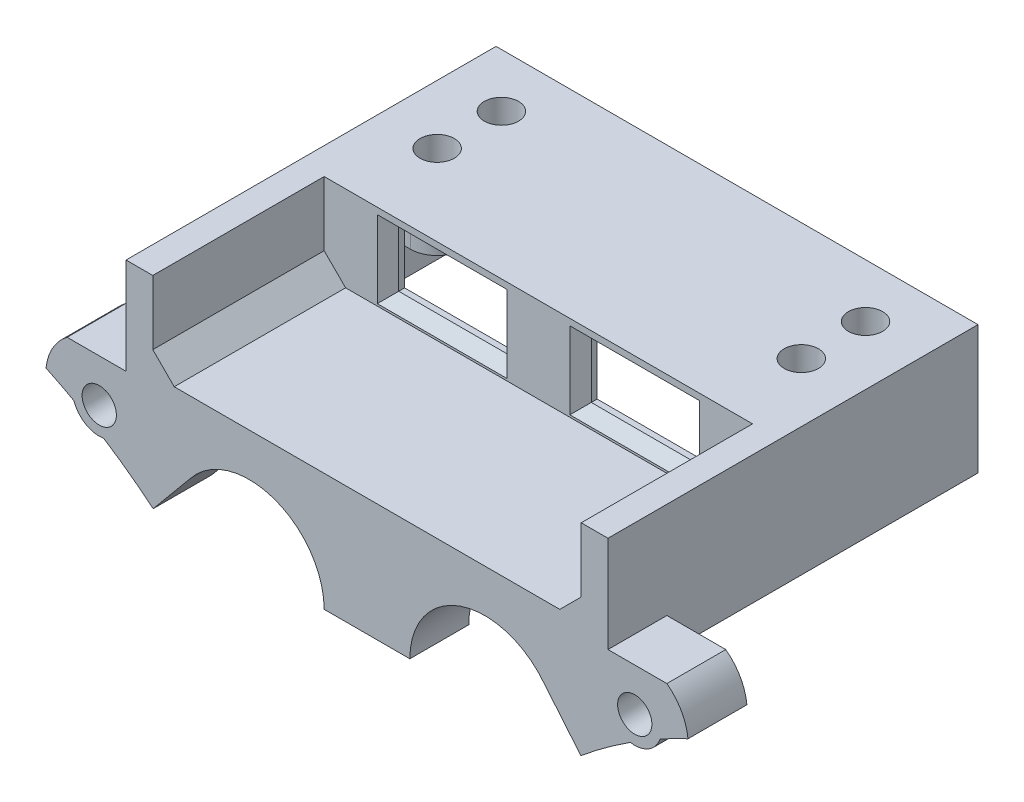
SolidWorks part; units mm, degrees
ref_plane "前视基准面" through (0, 0, 0) normal (0, 0, 1) x (1, 0, 0)
ref_plane "上视基准面" through (0, 0, 0) normal (0, 1, 0) x (1, 0, 0)
ref_plane "右视基准面" through (0, 0, 0) normal (1, 0, 0) x (0, 0, -1)
sketch "草图1" plane through (0, 0, 0) normal (0, 0, 1) x (1, 0, 0)
  line L0 (0, 0) -> (22.5, 0)
  line L1 (22.5, 0) -> (22.5, 12)
  line L2 (22.5, 12) -> (-22.5, 12)
  line L3 (-22.5, 12) -> (-22.5, 0)
  line L4 (-22.5, 0) -> (0, 0)
extrude "凸台-拉伸1" add sketch "草图1" along normal blind 34.55
sketch "草图2" plane through (0, 0, 34.55) normal (0, 0, 1) x (1, 0, 0)
  line L0 (-20, 12) -> (20, 12)
  line L1 (22.5, 12) -> (-22.5, 12) construction
  line L2 (20, 12) -> (20, 4)
  line L3 (20, 4) -> (-20, 4)
  line L4 (0, -6.6) -> (0, 6.6) construction
  line L5 (-20, 12) -> (-20, 4)
  point P9 (0, 4)
  point P10 (0, 12)
extrude "切除-拉伸1" cut sketch "草图2" against normal blind 16
sketch "草图3" plane through (0, 0, 0) normal (0, -1, 0) x (1, 0, 0)
  line L1 (0, 2) -> (20, 2)
  line L2 (20, 2) -> (20, 17)
  line L3 (20, 17) -> (-20, 17)
  line L4 (-20, 17) -> (-20, 2)
  line L5 (-20, 2) -> (0, 2)
extrude "切除-拉伸2" cut sketch "草图3" against normal blind 10
sketch "草图4" plane through (0, 0, 18.55) normal (0, 0, 1) x (1, 0, 0)
  line L0 (-14.04, 10.4) -> (-14.04, 5.2)
  line L1 (-13.94, 10.3) -> (-13.94, 5.3) construction
  line L7 (-13.94, 5.3) -> (-4.04, 5.3) construction
  line L8 (-13.94, 10.3) -> (-4.04, 10.3) construction
  line L9 (-4.04, 10.3) -> (-4.04, 5.3) construction
  line L10 (-14.04, 5.2) -> (-3.94, 5.2)
  line L11 (-3.94, 10.4) -> (-3.94, 5.2)
  line L12 (-14.04, 10.4) -> (-3.94, 10.4)
  line L13 (0, -6.6) -> (0, 6.6) construction
  line L14 (4.04, 10.3) -> (4.04, 5.3) construction
  line L15 (13.94, 10.3) -> (4.04, 10.3) construction
  line L16 (13.94, 5.3) -> (4.04, 5.3) construction
  line L17 (13.94, 10.3) -> (13.94, 5.3) construction
  line L18 (14.04, 10.4) -> (3.94, 10.4)
  line L19 (3.94, 10.4) -> (3.94, 5.2)
  line L20 (14.04, 5.2) -> (3.94, 5.2)
  line L21 (14.04, 10.4) -> (14.04, 5.2)
  dimension "D1" = 0.1
extrude "切除-拉伸3" cut sketch "草图4" against normal blind 10
chamfer "倒角1" distance 2 angle 45 2 edges at (20, 4, 26.55) (-20, 4, 26.55)
chamfer "倒角2" distance 1 angle 45 8 edges at (-8.99, 5.2, 18.55) (-14.04, 7.8, 18.55) (-8.99, 10.4, 18.55) (-3.94, 7.8, 18.55) (8.99, 10.4, 18.55) (3.94, 7.8, 18.55) (8.99, 5.2, 18.55) (14.04, 7.8, 18.55)
sketch "草图6" plane through (0, 12, 0) normal (0, 1, 0) x (1, 0, 0)
  line L0 (22.5, 0) -> (22.5, -13.5)
  line L2 (22.5, -34.55) -> (22.5, 0) construction
  line L3 (22.5, -13.5) -> (17, -13.5)
  line L4 (14.5, -11) -> (14.5, -5)
  line L5 (14.5, -5) -> (14.5, 0)
  line L6 (22.5, 0) -> (-22.5, 0) construction
  line L7 (14.5, 0) -> (22.5, 0)
  line L8 (0, -6.6) -> (0, 6.6) construction
  line L9 (-14.5, 0) -> (-22.5, 0)
  line L10 (-14.5, -5) -> (-14.5, 0)
  line L11 (-14.5, -11) -> (-14.5, -5)
  line L12 (-22.5, -13.5) -> (-17, -13.5)
  line L13 (-22.5, 0) -> (-22.5, -13.5)
  circle A0 centre (17, -5) radius 1.6
  circle A1 centre (17, -11) radius 1.6
  arc A2 (17, -13.5) -> (14.5, -11) centre (17, -11) cw
  arc A3 (-17, -13.5) -> (-14.5, -11) centre (-17, -11) ccw
  circle A4 centre (-17, -11) radius 1.6
  circle A5 centre (-17, -5) radius 1.6
extrude "凸台-拉伸2" add sketch "草图6" against normal blind 6.9
sketch "草图7" plane through (0, 12, 0) normal (0, 1, 0) x (1, 0, 0)
  circle A0 centre (17, -5) radius 1.6
  circle A1 centre (17, -11) radius 1.6
  circle A2 centre (-17, -5) radius 1.6
  circle A3 centre (-17, -11) radius 1.6
extrude "切除-拉伸4" cut sketch "草图7" against normal blind 10
sketch "草图8" plane through (0, 0, 34.55) normal (0, 0, 1) x (1, 0, 0)
  line L1 (1.843, -25.3671) -> (9.2306, -19.6151)
  line L2 (-18, 4) -> (18, 4) construction
  line L3 (0, -6.6) -> (0, 6.6) construction
  line L5 (16.5232, -2.6996) -> (19.968, -6.8465)
  line L6 (-1.843, -25.3671) -> (-9.2306, -19.6151)
  line L7 (-5.4768, -11.3004) -> (-10.4216, -17.6514)
  line L8 (5.4768, -11.3004) -> (10.4216, -17.6514)
  line L9 (-16.5232, -2.6996) -> (-19.968, -6.8465)
  line L10 (22.5, 3) -> (22.5, 4)
  line L11 (-22.5, 12) -> (-22.5, 0) construction
  line L12 (-22.5, 3) -> (-28, 3)
  line L13 (-22.5, 3) -> (-22.5, 4)
  line L14 (22.5, 3) -> (28, 3)
  line L15 (-22.5, 4) -> (22.5, 4)
  circle A1 centre (25, -1) radius 1.6
  circle A3 centre (0, -23) radius 1.6
  arc A4 (-1.843, -25.3671) -> (1.843, -25.3671) centre (0, -23) ccw
  circle A6 centre (-25, -1) radius 1.6
  arc A8 (29.9729, -0.4804) -> (27.3654, -1.8093) centre (50, -43) ccw
  arc A9 (10.4216, -17.6514) -> (9.2306, -19.6151) centre (50, -43) ccw
  arc A10 (16.5232, -2.6996) -> (5.4768, -11.3004) centre (11, -7) ccw
  arc A11 (24.5837, -3.4651) -> (27.3654, -1.8093) centre (25, -1) ccw
  arc A12 (24.5837, -3.4651) -> (19.968, -6.8465) centre (50, -43) ccw
  arc A13 (-10.4216, -17.6514) -> (-9.2306, -19.6151) centre (-50, -43) cw
  arc A14 (-16.5232, -2.6996) -> (-5.4768, -11.3004) centre (-11, -7) cw
  arc A15 (-24.5837, -3.4651) -> (-19.968, -6.8465) centre (-50, -43) cw
  arc A16 (-24.5837, -3.4651) -> (-27.3654, -1.8093) centre (-25, -1) cw
  arc A17 (-29.9729, -0.4804) -> (-27.3654, -1.8093) centre (-50, -43) cw
  arc A18 (-29.9729, -0.4804) -> (-28, 3) centre (-25, -1) cw
  arc A19 (29.9729, -0.4804) -> (28, 3) centre (25, -1) ccw
  point P23 (0, 4)
extrude "凸台-拉伸3" add sketch "草图8" against normal blind 5.5
sketch "草图10" plane through (0, 0, 0) normal (0, 0, -1) x (-1, 0, 0)
  line L1 (22.5, 0) -> (-22.5, 0) construction
  line L2 (-20, 0) -> (-20, 10)
  line L3 (-20, 10) -> (20, 10)
  line L4 (20, 10) -> (20, 0)
  line L5 (20, 0) -> (-20, 0)
extrude "切除-拉伸5" cut sketch "草图10" against normal blind 2
sketch "草图11" plane through (0, 0, 29.05) normal (0, 0, -1) x (-1, 0, 0)
  line L0 (-4, -7) -> (4, -7)
  line L1 (-4, -7) -> (-10.4216, -17.6514)
  line L2 (-10.4216, -17.6514) -> (-10.4216, -27.0892)
  line L3 (-10.4216, -27.0892) -> (10.4216, -27.0892)
  line L4 (0, 19.0025) -> (0, -19.0025) construction
  line L5 (10.4216, -17.6514) -> (10.4216, -27.0892)
  line L6 (4, -7) -> (10.4216, -17.6514)
  arc A0 (-5.4768, -11.3004) -> (-11, 0) centre (-11, -7) ccw construction
  arc A1 (11, 0) -> (5.4768, -11.3004) centre (11, -7) ccw construction
  point P16 (0, -27.0892)
extrude "切除-拉伸6" cut sketch "草图11" against normal blind 10
